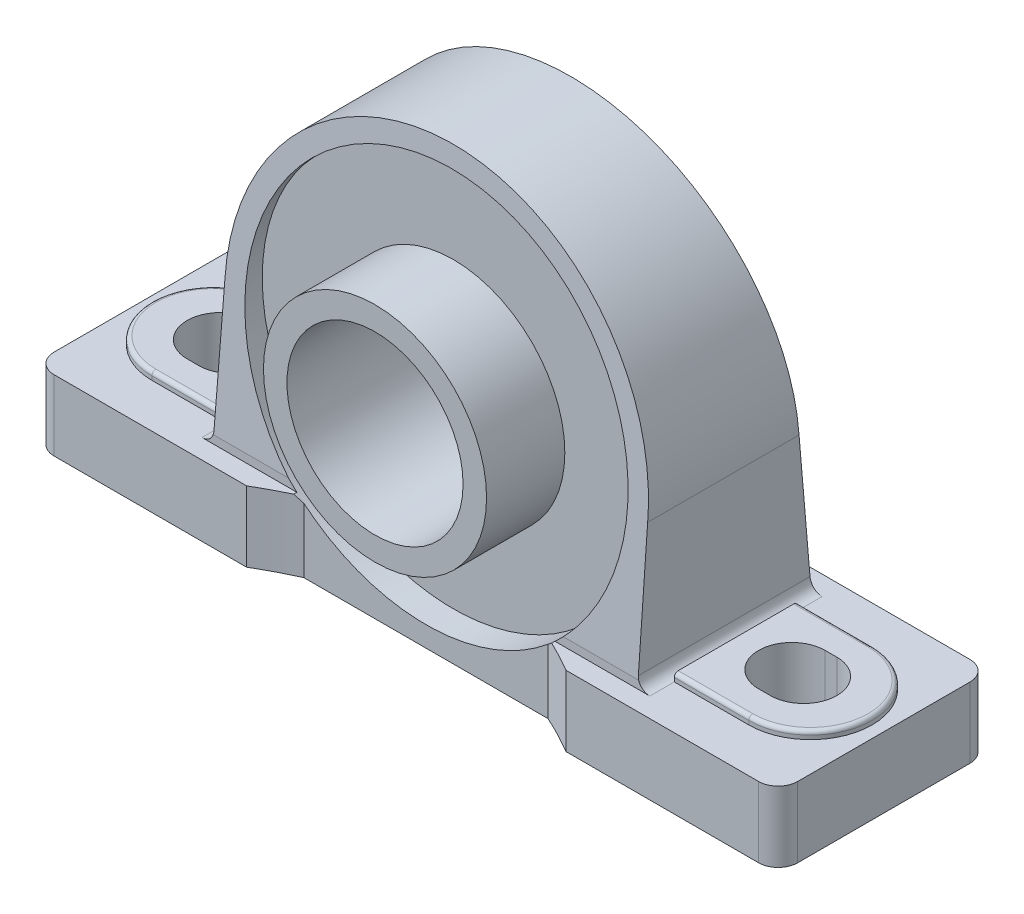
SolidWorks part; units mm, degrees
ref_plane "Front Plane" through (0, 0, 0) normal (0, 0, 1) x (1, 0, 0)
ref_plane "Top Plane" through (0, 0, 0) normal (0, 1, 0) x (1, 0, 0)
ref_plane "Right Plane" through (0, 0, 0) normal (1, 0, 0) x (0, 0, -1)
sketch "Sketch1" plane through (0, 0, 0) normal (0, 0, 1) x (1, 0, 0)
  line L1 (-95, 18) -> (95, 18)
  line L2 (-95, 18) -> (-95, 0)
  line L3 (-95, 0) -> (95, 0)
  line L4 (95, 18) -> (95, 0)
  point P4 (0, 0)
  dimension "D1" = 190
  dimension "D2" = 18
extrude "Boss-Extrude1" add sketch "Sketch1" along normal mid plane 54
fillet "Fillet1" radius 5 4 edges at (-95, 9, -27) (-95, 9, 27) (95, 9, -27) (95, 9, 27)
sketch "Sketch3" plane through (0, 18, 0) normal (0, 1, 0) x (1, 0, 0)
  line L0 (-40.8197, 27) -> (-40.8197, -27) construction
  line L1 (0, 0) -> (0, -9.4497) construction
  line L2 (40.8197, 27) -> (40.8197, -27) construction
  line L3 (0, 0) -> (-17.4106, 0) construction
  line L6 (-40.8197, 27) -> (40.8197, 27)
  line L7 (-40.8197, -27) -> (40.8197, -27)
  spline S0 degree 2 poles (-40.8197, 27) (0, 3) (40.8197, 27) knots 0 0 0 1 1 1
  spline S1 degree 2 poles (-40.8197, -27) (0, -3) (40.8197, -27) knots 0 0 0 1 1 1
  dimension "D1" = 30
extrude "Cut-Extrude1" cut sketch "Sketch3" against normal blind 54
sketch "Sketch4" plane through (0, 0, 0) normal (0, 0, 1) x (1, 0, 0)
  line L0 (-40.8197, 0) -> (40.8197, 0) construction
  circle A0 centre (0, 54) radius 54
  dimension "D1" = 54
extrude "Boss-Extrude3" add sketch "Sketch4" along normal mid plane 44 separate body
sketch "Sketch6" plane through (0, 0, 0) normal (0, 0, 1) x (1, 0, 0)
  line L0 (-53.9976, 53.4886) -> (-54.3469, 0)
  line L1 (0, 54) -> (0, 32.1729) construction
  line L2 (53.9976, 53.4886) -> (54.3469, 0)
  line L3 (-54.3469, 0) -> (54.3469, 0)
  circle A0 centre (0, 54) radius 54 construction
  arc A1 (-53.9976, 53.4886) -> (53.9976, 53.4886) centre (0, 54) ccw
extrude "Boss-Extrude4" add sketch "Sketch6" along normal mid plane 44 contours A1 L0 L3 | A1 L3 L2
sketch "Sketch7" plane through (0, 0, 0) normal (1, 0, 0) x (0, 0, -1)
  line L0 (-22.166, 18) -> (-15, 108)
  line L1 (-15, 108) -> (-33.4723, 108)
  line L2 (-33.4723, 108) -> (-33.4723, 18)
  line L3 (-33.4723, 18) -> (-22.166, 18)
  line L4 (0, 98.3402) -> (0, 53.4886) construction
  line L9 (-22, 18) -> (-27, 18) construction
  line L10 (-22, 53.4886) -> (22, 53.4886) construction
  line L11 (33.4723, 18) -> (22.166, 18)
  line L12 (33.4723, 108) -> (33.4723, 18)
  line L13 (15, 108) -> (33.4723, 108)
  line L14 (22.166, 18) -> (15, 108)
  point P8 (0, 53.4886)
  dimension "D1" = 30
extrude "Cut-Extrude2" cut sketch "Sketch7" against normal mid plane 164
sketch "Sketch8" plane through (0, 0, 0) normal (0, 0, 1) x (1, 0, 0)
  circle A0 centre (0, 54) radius 22.5
  dimension "D1" = 45
  dimension "D2" = 54
extrude "Cut-Extrude3" cut sketch "Sketch8" against normal mid plane 164
sketch "Sketch9" plane through (0, 0, 0) normal (0, 0, 1) x (1, 0, 0)
  circle A0 centre (0, 54) radius 48.8093
  dimension "D1" = 54
extrude "Cut-Extrude4" cut sketch "Sketch9" against normal blind 164 from offset 15 offset against normal yes
mirror "Mirror1" about plane through (0, 0, 0) normal (0, 0, 1) of "Cut-Extrude4"
sketch "Sketch10" plane through (0, 0, 0) normal (0, 0, 1) x (1, 0, 0)
  line L0 (0, 0) -> (0, 54) construction
  circle A0 centre (0, 54) radius 22.5
  circle A1 centre (0, 54) radius 28.5
  dimension "D1" = 6
  dimension "D2" = 54
extrude "Boss-Extrude5" add sketch "Sketch10" along normal blind 35
sketch "Sketch11" plane through (0, 0, -15) normal (0, 0, -1) x (-1, 0, 0)
  circle A0 centre (0, 54) radius 22.5 construction
  circle A1 centre (0, 54) radius 22.5
  circle A2 centre (0, 54) radius 28.5
  dimension "D1" = 6
extrude "Boss-Extrude6" add sketch "Sketch11" along normal blind 2 separate body
fillet "Fillet2" radius 3 2 edges at (54.2293, 18, 0) (-54.2293, 18, 0)
sketch "Sketch12" plane through (0, 18, 0) normal (0, 1, 0) x (1, 0, 0)
  line L0 (-95, -22) -> (-95, 22) construction
  line L1 (-76.25, 15.75) -> (-57.2098, 15.75)
  line L2 (-76.25, -15.75) -> (-57.2098, -15.75)
  line L3 (-57.2098, 15.75) -> (-57.2098, -15.75)
  line L4 (-57.2098, -22) -> (-57.2098, 22) construction
  line L5 (95, 0) -> (75.3625, 0) construction
  line L6 (-95, 0) -> (-75.3625, 0) construction
  line L7 (-76.25, 15.75) -> (-57.2098, 15.75)
  line L8 (-76.25, 15.75) -> (-57.2098, 15.75)
  line L12 (-74.5, 0) -> (-71.5, 0) construction
  line L13 (-74.5, 8.5) -> (-71.5, 8.5)
  line L14 (-74.5, -8.5) -> (-71.5, -8.5)
  line L15 (-76.25, 15.75) -> (-57.2098, 15.75)
  line L16 (-76.25, -15.75) -> (-57.2098, -15.75)
  line L17 (-76.25, -15.75) -> (-57.2098, -15.75)
  line L18 (-76.25, 15.75) -> (-57.2098, 15.75)
  line L19 (-76.25, -15.75) -> (-57.2098, -15.75)
  line L20 (0, -15.0019) -> (0, 36.8272) construction
  line L21 (-76.25, -15.75) -> (-57.2098, -15.75)
  line L22 (-76.25, 15.75) -> (-57.2098, 15.75)
  line L23 (-76.25, 15.75) -> (-57.2098, 15.75)
  line L24 (-76.25, -15.75) -> (-57.2098, -15.75)
  line L25 (-76.25, -15.75) -> (-57.2098, -15.75)
  line L26 (-76.25, 15.75) -> (-57.2098, 15.75)
  line L30 (-76.25, -15.75) -> (-57.2098, -15.75)
  line L31 (76.25, -15.75) -> (57.2098, -15.75)
  line L32 (76.25, 15.75) -> (57.2098, 15.75)
  line L33 (76.25, -15.75) -> (57.2098, -15.75)
  line L34 (76.25, -15.75) -> (57.2098, -15.75)
  line L35 (76.25, 15.75) -> (57.2098, 15.75)
  line L36 (76.25, 15.75) -> (57.2098, 15.75)
  line L37 (76.25, -15.75) -> (57.2098, -15.75)
  line L38 (76.25, -15.75) -> (57.2098, -15.75)
  line L39 (76.25, 15.75) -> (57.2098, 15.75)
  line L40 (76.25, -15.75) -> (57.2098, -15.75)
  line L41 (76.25, -15.75) -> (57.2098, -15.75)
  line L42 (76.25, 15.75) -> (57.2098, 15.75)
  line L43 (76.25, 15.75) -> (57.2098, 15.75)
  line L44 (76.25, 15.75) -> (57.2098, 15.75)
  line L45 (57.2098, 15.75) -> (57.2098, -15.75)
  line L46 (76.25, -15.75) -> (57.2098, -15.75)
  line L47 (76.25, 15.75) -> (57.2098, 15.75)
  line L48 (74.5, 0) -> (71.5, 0) construction
  line L49 (74.5, 8.5) -> (71.5, 8.5)
  line L50 (74.5, -8.5) -> (71.5, -8.5)
  arc A0 (-76.25, 15.75) -> (-76.25, -15.75) centre (-76.25, 0) ccw
  arc A2 (-74.5, 8.5) -> (-74.5, -8.5) centre (-74.5, 0) ccw
  arc A3 (-71.5, -8.5) -> (-71.5, 8.5) centre (-71.5, 0) ccw
  arc A4 (76.25, 15.75) -> (76.25, -15.75) centre (76.25, 0) cw
  arc A5 (74.5, 8.5) -> (74.5, -8.5) centre (74.5, 0) cw
  arc A6 (71.5, -8.5) -> (71.5, 8.5) centre (71.5, 0) cw
  point P2 (-92, 0)
  point P9 (-95, 0)
  point P24 (-73, 0)
  point P29 (-63, 0)
  point P30 (-83, 0)
  point P33 (73, 0)
  point P39 (-73, 8.5)
  dimension "D1" = 31.5
  dimension "D2" = 3
  dimension "D3" = 17
  dimension "D4" = 20
  dimension "D5" = 73
extrude "Boss-Extrude7" add sketch "Sketch12" along normal blind 2
sketch "Sketch13" plane through (0, 18, 0) normal (0, 1, 0) x (1, 0, 0)
  line L0 (-74.5, 8.5) -> (-71.5, 8.5) construction
  line L1 (-74.5, -8.5) -> (-71.5, -8.5) construction
  line L2 (-74.5, -8.5) -> (-71.5, -8.5)
  line L3 (-74.5, 8.5) -> (-71.5, 8.5)
  line L4 (0, 0) -> (0, 39.4765) construction
  line L7 (74.5, -8.5) -> (71.5, -8.5) construction
  line L8 (74.5, 8.5) -> (71.5, 8.5) construction
  line L9 (74.5, -8.5) -> (71.5, -8.5)
  line L10 (74.5, 8.5) -> (71.5, 8.5)
  arc A0 (-71.5, -8.5) -> (-71.5, 8.5) centre (-71.5, 0) ccw construction
  arc A1 (-74.5, 8.5) -> (-74.5, -8.5) centre (-74.5, 0) ccw construction
  arc A2 (-71.5, -8.5) -> (-71.5, 8.5) centre (-71.5, 0) ccw
  arc A3 (-74.5, 8.5) -> (-74.5, -8.5) centre (-74.5, 0) ccw
  arc A6 (74.5, -8.5) -> (74.5, 8.5) centre (74.5, 0) ccw construction
  arc A7 (71.5, 8.5) -> (71.5, -8.5) centre (71.5, 0) ccw construction
  arc A8 (74.5, -8.5) -> (74.5, 8.5) centre (74.5, 0) ccw
  arc A9 (71.5, 8.5) -> (71.5, -8.5) centre (71.5, 0) ccw
extrude "Cut-Extrude5" cut sketch "Sketch13" against normal blind 52.5
fillet "Fillet3" radius 1 6 edges at (92, 20, 0) (-66.7299, 20, -15.75) (-66.7299, 20, 15.75) (-92, 20, 0) (66.7299, 20, -15.75) (66.7299, 20, 15.75)
